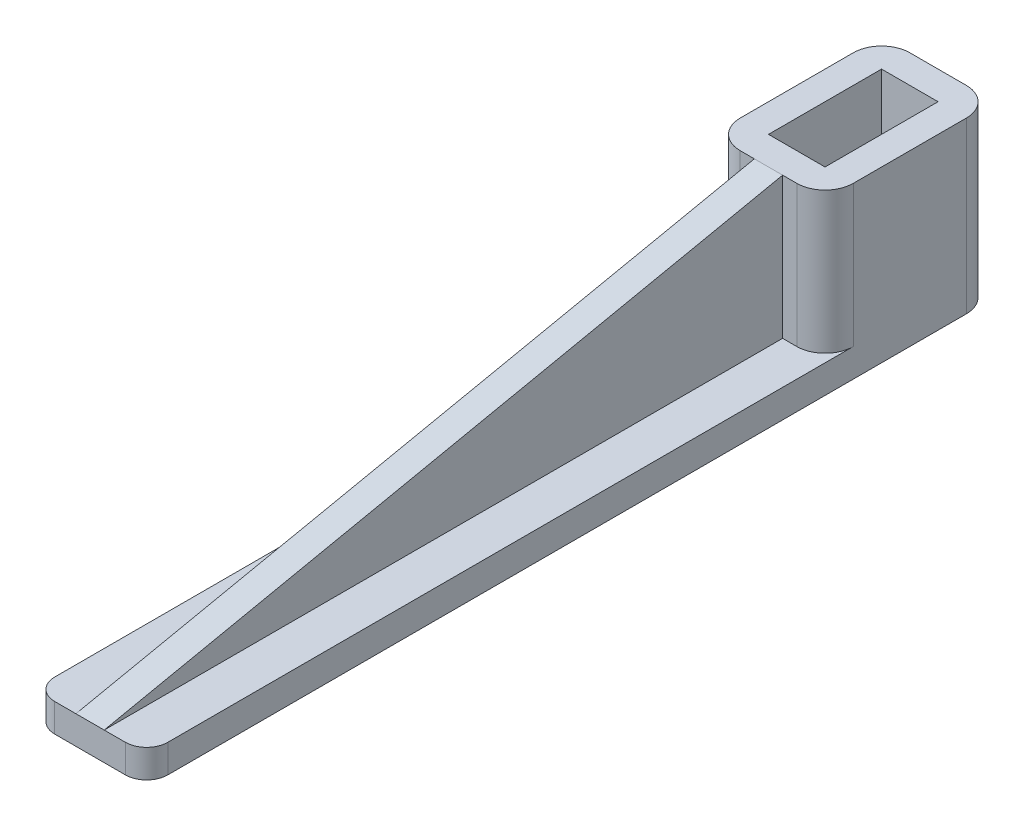
SolidWorks part; units mm, degrees
ref_plane "Спереди" through (0, 0, 0) normal (0, 0, 1) x (1, 0, 0)
ref_plane "Сверху" through (0, 0, 0) normal (0, 1, 0) x (1, 0, 0)
ref_plane "Справа" through (0, 0, 0) normal (1, 0, 0) x (0, 0, -1)
sketch "Эскиз1" plane through (0, 0, 0) normal (0, 1, 0) x (1, 0, 0)
  line L0 (0, 11.0085) -> (0, -20.1186) construction
  line L1 (-10, 15) -> (10, 15)
  line L2 (5, 10) -> (-5, 10)
  line L3 (5, 10) -> (5, -10)
  line L4 (5, -10) -> (-5, -10)
  line L5 (-5, 10) -> (-5, -10)
  line L6 (5, 10) -> (-5, -10) construction
  line L7 (5, -10) -> (-5, 10) construction
  line L8 (10, 15) -> (10, -135)
  line L9 (10, -135) -> (-10, -135)
  line L10 (-10, -135) -> (-10, 15)
  line L11 (-10, -15) -> (10, -15)
  point P1 (0, 0)
  point P10 (0, 15)
  dimension "D1" = 10
  dimension "D2" = 20
  dimension "D3" = 5
  dimension "D4" = 5
  dimension "D5" = 150
  dimension "D6" = 5
extrude "Бобышка-Вытянуть1" add sketch "Эскиз1" along normal blind 30 contours L10 L11 L8 L1 L5 L2 L3 L4 region at (0, 0, -14.6394)
extrude "Бобышка-Вытянуть2" add sketch "Эскиз1<3>" along normal blind 5 contours L11 L10 L9 L8 region at (0, 0, 75)
sketch "Эскиз1<3>" plane through (0, 0, 0) normal (0, 1, 0) x (1, 0, 0) same geometry as "Эскиз1"
sketch "Эскиз2" plane through (0, 0, 0) normal (1, 0, 0) x (0, 0, -1)
  line L0 (-135, 5) -> (-15, 30)
rib "Ребро1" sketch "Эскиз2" sketch "Эскиз2" thickness 5 extrusion direction parallel to sketch draft on no parameters "D1"=5
fillet "Скругление1" radius 5 4 edges at (-10, 17.5, 15) (-10, 15, -15) (10, 15, -15) (10, 17.5, 15)
fillet "Скругление3" radius 3.75 2 edges at (-10, 2.5, 135) (10, 2.5, 135)
fillet "Скругление2" [suppressed] radius 2.5
